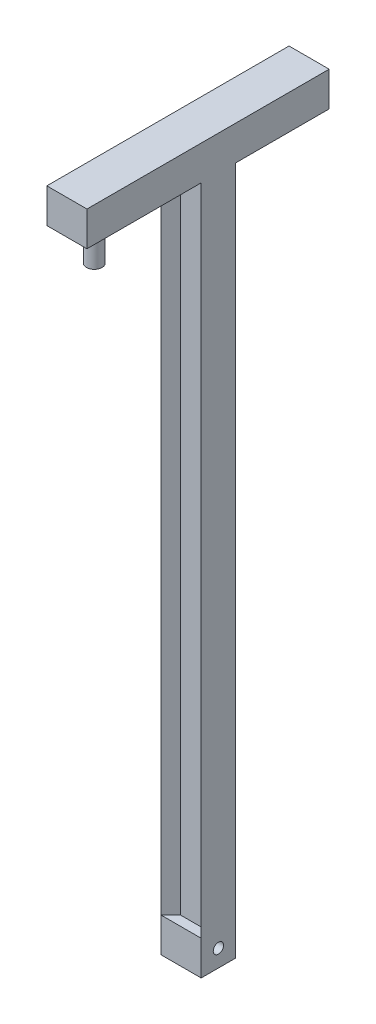
SolidWorks part; units mm, degrees
ref_plane "Front Plane" through (0, 0, 0) normal (0, 0, 1) x (1, 0, 0)
ref_plane "Top Plane" through (0, 0, 0) normal (0, 1, 0) x (1, 0, 0)
ref_plane "Right Plane" through (0, 0, 0) normal (1, 0, 0) x (0, 0, -1)
sketch "Sketch1" plane through (0, 0, 0) normal (0, 1, 0) x (1, 0, 0)
  line L0 (0, 0) -> (-2.8284, -2.8284)
  line L1 (-2.8284, -2.8284) -> (-8.8284, -2.8284)
  line L2 (-8.8284, -2.8284) -> (-11.6569, 0)
  line L3 (-11.6569, 0) -> (-11.6569, -10)
  line L4 (-11.6569, -10) -> (-8.8284, -7.1716)
  line L5 (-8.8284, -7.1716) -> (-2.8284, -7.1716)
  line L6 (-2.8284, -7.1716) -> (0, -10)
  line L7 (0, -10) -> (0, 0)
  dimension "D1" = 6
  dimension "D2" = 6
  dimension "D3" = 135
  dimension "D4" = 135
  dimension "D5" = 10
  dimension "D6" = 10
  dimension "D7" = 4
  dimension "D8" = 4
extrude "Boss-Extrude1" add sketch "Sketch1" along normal blind 200
sketch "Sketch2" plane through (0, 0, 0) normal (0, -1, 0) x (1, 0, 0)
  line L1 (0, 0) -> (-11.6569, 0)
  line L2 (0, 0) -> (0, 10)
  line L3 (0, 10) -> (-11.6569, 10)
  line L4 (-11.6569, 0) -> (-11.6569, 10)
extrude "Boss-Extrude2" add sketch "Sketch2" along normal blind 10
sketch "Sketch3" plane through (-11.6569, 0, 0) normal (-1, 0, 0) x (0, 0, 1)
  line L0 (10, -10) -> (0, -10) construction
  line L2 (0, -10) -> (0, 0) construction
  circle A0 centre (5, -5) radius 1.5
  point P4 (5, -10)
  point P7 (0, -5)
  dimension "D1" = 0
  dimension "D2" = 0
  dimension "D3" = 3
extrude "Cut-Extrude1" cut sketch "Sketch3" against normal blind 30
sketch "Sketch4" plane through (0, 0, 2.8284) normal (0, 0, -1) x (-1, 0, 0)
  line L0 (0, 200) -> (0, 0) construction
  line L1 (0, 200) -> (11.6569, 200)
  line L2 (0, 200) -> (0, 190)
  line L3 (0, 190) -> (11.6569, 190)
  line L4 (11.6569, 200) -> (11.6569, 190)
  line L5 (11.6569, 200) -> (11.6569, 0) construction
  line L6 (2.8284, 200) -> (8.8284, 200) construction
  dimension "D1" = 0
  dimension "D2" = 0
  dimension "D3" = 0
  dimension "D4" = 10
extrude "Boss-Extrude3" add sketch "Sketch4" along normal blind 30
sketch "Sketch5" plane through (0, 0, 7.1716) normal (0, 0, 1) x (1, 0, 0)
  line L0 (0, 200) -> (0, 0) construction
  line L1 (0, 200) -> (-11.6569, 200)
  line L2 (0, 200) -> (0, 190)
  line L3 (0, 190) -> (-11.6569, 190)
  line L4 (-11.6569, 200) -> (-11.6569, 190)
  line L5 (-8.8284, 200) -> (-2.8284, 200) construction
  dimension "D1" = 0
  dimension "D2" = 0
  dimension "D3" = 0
  dimension "D4" = 10
extrude "Boss-Extrude4" add sketch "Sketch5" along normal blind 36
sketch "Sketch7" plane through (0, 190, 0) normal (0, -1, 0) x (1, 0, 0)
  line L0 (-11.6569, 43.1716) -> (0, 43.1716) construction
  circle A0 centre (-8.335, 32.7116) radius 2.25
  dimension "D1" = 10.46
  dimension "D2" = 4.5
extrude "Boss-Extrude6" add sketch "Sketch7" along normal blind 13
sketch "Sketch8" plane through (0, 0, -27.1716) normal (0, 0, -1) x (-1, 0, 0)
  line L0 (0, 190) -> (11.6569, 190) construction
  line L1 (11.6569, 190) -> (11.6569, 200) construction
  circle A0 centre (5.8284, 195) radius 2.75
  point P4 (5.8284, 190)
  point P7 (11.6569, 195)
  dimension "D1" = 0
  dimension "D2" = 0
  dimension "D3" = 5.5
extrude "Cut-Extrude2" cut sketch "Sketch8" against normal blind 10
sketch "Sketch9" plane through (0, 190, 0) normal (0, -1, 0) x (-1, 0, 0)
  circle A0 centre (8.335, -32.7116) radius 3.5
  dimension "D1" = 7
extrude "Boss-Extrude7" add sketch "Sketch9" along normal blind 3
thread "Thread1" pitch 2.1167 method cut profile "Thread Profile1" start angle 0, offset 0, length 8, pitch 2.1167, diameter 5.5
ref_plane "Plane1" through (-3.0784, 195, -27.1716) normal (0, -1, 0) x (1, 0, 0)
sketch "Thread Profile1" plane through (-3.0784, 195, -27.1716) normal (0, -1, 0) x (1, 0, 0)
  line L0 (0, 0) -> (0, 2.1167) construction
  line L1 (0, 0) -> (1.1457, 0.6615)
  line L2 (1.1457, 0.6615) -> (1.1457, 0.926)
  line L3 (1.1457, 0.926) -> (0, 1.5875)
  line L4 (1.1457, 0.7937) -> (0, 0.7937) construction
  line L11 (0, 0) -> (0, 1.5875)
  point P2 (0, 0)
  dimension "Pitch" = 2.1167
  dimension "Profile_Angle" = 60
  dimension "Profile_Land" = 0.2646
  dimension "Profile_Height" = 1.1457
sketch "Sketch12" plane through (0, 0, -27.1716) normal (0, 0, -1) x (-1, 0, 0)
  circle A0 centre (5.8284, 195) radius 3.75
  dimension "D1" = 7.5
extrude "Cut-Extrude3" cut sketch "Sketch12" against normal blind 2
